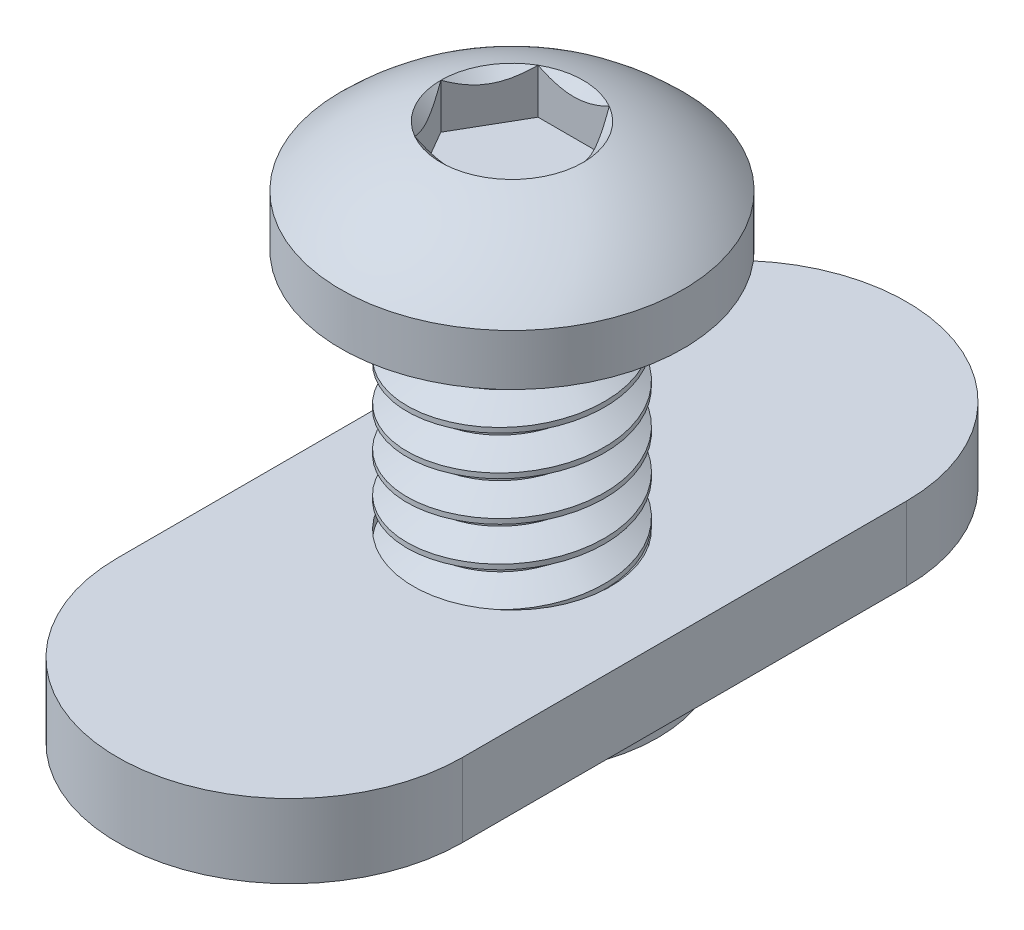
SolidWorks part; units mm, degrees
ref_plane "Front Plane" through (0, 0, 0) normal (0, 0, 1) x (1, 0, 0)
ref_plane "Top Plane" through (0, 0, 0) normal (0, 1, 0) x (1, 0, 0)
ref_plane "Right Plane" through (0, 0, 0) normal (1, 0, 0) x (0, 0, -1)
sketch "Sketch1" plane through (0, 0, 0) normal (0, 0, 1) x (1, 0, 0)
  line L0 (0, 0) -> (0, 53.1234) construction
  line L1 (0, 0) -> (-3.175, 0)
  line L2 (-3.175, 0) -> (-3.175, 12.7)
  line L3 (-3.175, 12.7) -> (-5.5118, 12.7)
  line L4 (-5.5118, 12.7) -> (-5.5118, 14.3459)
  line L5 (-5.5118, 14.3459) -> (-4.4094, 14.3459)
  line L6 (0, 0) -> (0, 16.8148)
  arc A0 (-4.4094, 14.3459) -> (0, 16.8148) centre (0, 11.6427) cw
  dimension "screw od" = 6.35
  dimension "head od" = 11.0236
  dimension "D3" = 8.8189
  dimension "D4" = 1.6459
  dimension "head height" = 4.1148
  dimension "screw length" = 12.7
sketch "Sketch2" plane through (0, 0, 0) normal (0, 0, 1) x (1, 0, 0)
  line L0 (0, 0) -> (0, 16.8148) construction
  line L1 (-3.175, 12.7) -> (-5.5118, 12.7) construction
  line L2 (0, 0) -> (-3.175, 0) construction
  line L3 (-3.175, 0) -> (-3.175, 12.7) construction
  line L4 (0, 0) -> (0, 12.7)
  line L5 (0, 12.7) -> (-3.175, 12.7)
  line L6 (0, 0) -> (-3.175, 0)
  line L7 (-3.175, 0) -> (-3.175, 12.7)
revolve "Revolve2" add sketch "Sketch2" angle 360 about L0
sketch "Sketch3" plane through (0, 12.7, 0) normal (0, 1, 0) x (1, 0, 0)
  circle A1 centre (0, 0) radius 3.175
  circle A2 centre (0, 0) radius 3.175
  dimension "D1" = 0
curve "Helix/Spiral1" pitch 1.27 height 17.4625 turns 13.75 parameters "pitch"=1.27
chamfer "Chamfer1" distance 1.27 angle 45 1 edges at (0, 0, -3.175)
sketch "Sketch4" plane through (0, 0, 0) normal (0, 0, 1) x (1, 0, 0)
  line L0 (3.175, 13.8112) -> (3.175, 12.7)
  line L1 (3.175, 12.7) -> (2.3501, 13.1762)
  line L2 (2.3501, 13.1762) -> (2.3501, 13.335)
  line L3 (2.3501, 13.335) -> (3.175, 13.8112)
  line L4 (2.3501, 13.2556) -> (3.175, 13.2556) construction
  line L5 (2.7626, 12.9381) -> (2.7626, 13.5731) construction
  line L7 (3.175, 12.7) -> (-3.175, 12.7) construction
  dimension "D1" = 60
  dimension "D2" = 0.1588
  dimension "D3" = 0.635
sweep "Cut-Sweep1" cut profiles "Sketch4" path "Helix/Spiral1"
sketch "Sketch5" plane through (0, 0, 0) normal (0, 0, 1) x (1, 0, 0)
  line L0 (0, 0) -> (0, 16.8148) construction
  line L1 (-3.175, 12.7) -> (-5.5118, 12.7) construction
  line L2 (-5.5118, 14.3459) -> (-4.4094, 14.3459) construction
  line L3 (-5.5118, 12.7) -> (-5.5118, 14.3459) construction
  line L4 (0, 12.7) -> (0, 16.8148)
  line L5 (0, 12.7) -> (-5.5118, 12.7)
  line L6 (-5.5118, 14.3459) -> (-4.4094, 14.3459)
  line L7 (-5.5118, 12.7) -> (-5.5118, 14.3459)
  arc A0 (0, 16.8148) -> (-4.4094, 14.3459) centre (0, 11.6427) ccw construction
  arc A1 (0, 16.8148) -> (-4.4094, 14.3459) centre (0, 11.6427) ccw
revolve "Revolve3" add sketch "Sketch5" angle 360 about L0
ref_plane "Plane1" through (0, 16.8148, 0) normal (0, 1, 0) x (-1, 0, 0)
sketch "Sketch6" plane through (0, 16.8148, 0) normal (0, 1, 0) x (-1, 0, 0)
  line L1 (1.1457, 1.9844) -> (-1.1457, 1.9844)
  line L2 (-1.1457, 1.9844) -> (-2.2914, 0)
  line L3 (-2.2914, 0) -> (-1.1457, -1.9844)
  line L4 (-1.1457, -1.9844) -> (1.1457, -1.9844)
  line L5 (1.1457, -1.9844) -> (2.2914, 0)
  line L6 (2.2914, 0) -> (1.1457, 1.9844)
  circle A0 centre (0, 0) radius 1.9844 construction
  dimension "hex" = 3.9688
extrude "Cut-Extrude1" cut sketch "Sketch6" against normal blind 1.9844
ref_plane "Plane2" through (0, 16.2795, 0) normal (0, 1, 0) x (-1, 0, 0)
sketch "Sketch7" plane through (0, 16.2795, 0) normal (0, 1, 0) x (-1, 0, 0)
  circle A0 centre (0, 0) radius 2.2914
extrude "Cut-Extrude2" cut sketch "Sketch7" against normal up to surface (1.4491 mm away) draft 45 and the other way through all
ref_plane "Plane3" through (0, 3.175, 0) normal (0, -1, 0) x (1, 0, 0)
sketch "Sketch8" plane through (0, 3.175, 0) normal (0, -1, 0) x (1, 0, 0)
  line L0 (0, -7.1437) -> (0, 7.1437) construction
  line L2 (-5.5563, 7.1437) -> (-5.5563, -7.1437)
  line L4 (5.5563, 7.1437) -> (5.5563, -7.1437)
  circle A0 centre (0, 0) radius 3.175
  arc A1 (-5.5563, 7.1437) -> (5.5563, 7.1437) centre (0, 7.1437) cw
  arc A2 (-5.5563, -7.1437) -> (5.5563, -7.1437) centre (0, -7.1437) ccw
  dimension "D1" = 6.35
  dimension "D3" = 25.4
  dimension "D2" = 11.1125
extrude "Extrude1" add sketch "Sketch8" along normal mid plane 3.4544 separate body
sketch "Sketch9" plane through (0, 1.4478, 0) normal (0, -1, 0) x (1, 0, 0)
  line L2 (5.5563, -7.1437) -> (5.5563, 7.1437)
  line L3 (-5.5563, 7.1437) -> (-5.5563, -7.1437)
  line L4 (5.5563, -7.1437) -> (5.5563, 7.1437)
  line L5 (-5.5563, 7.1437) -> (-5.5563, -7.1437)
  arc A2 (-5.5563, -7.1437) -> (5.5563, -7.1437) centre (0, -7.1437) ccw
  arc A3 (5.5563, 7.1437) -> (-5.5563, 7.1437) centre (0, 7.1437) ccw
  arc A4 (-5.5563, -7.1437) -> (5.5563, -7.1437) centre (0, -7.1437) ccw
  arc A5 (5.5563, 7.1437) -> (-5.5563, 7.1437) centre (0, 7.1437) ccw
  circle A6 centre (0, 0) radius 4.699
  circle A7 centre (0, 0) radius 4.699
  dimension "D1" = 0
  dimension "D2" = 1.524
extrude "Cut-Extrude3" cut sketch "Sketch9" against normal offset from surface (1.0795 mm away) 2.3749 up to face at (0, 4.9022, 0)
sketch "Sketch10" [suppressed] plane through (0, 7.9375, 0) normal (0, -1, 0) x (1, 0, 0)
  line L0 (-8.255, -12.3888) -> (-8.255, 2.8511)
  line L1 (8.255, 2.8511) -> (8.255, -12.3888)
  line L2 (-14.9844, 7.9311) -> (0, 7.9311) construction
  circle A0 centre (0, 0) radius 3.9688
  arc A1 (8.255, 2.8511) -> (-8.255, 2.8511) centre (0, -1.316) ccw
  arc A2 (-8.255, -12.3888) -> (8.255, -12.3888) centre (0, -8.2217) ccw
  dimension "D2" = 3.9624
  dimension "D3" = 16.51
  dimension "D4" = 5.08
  dimension "D5" = 6.35
  dimension "D1" = 25.4
extrude "Extrude2" [suppressed] add sketch "Sketch10" along normal mid plane 5.3594 separate body
sketch "Sketch11" [suppressed] plane through (0, 5.2578, 0) normal (0, -1, 0) x (1, 0, 0)
  line L2 (8.255, -12.3888) -> (8.255, 2.8511)
  line L3 (-8.255, 2.8512) -> (-8.255, -12.3888)
  line L4 (8.255, -12.3888) -> (8.255, 2.8511)
  line L5 (-8.255, 2.8512) -> (-8.255, -12.3888)
  circle A2 centre (0, 0) radius 5.4927
  circle A3 centre (0, 0) radius 5.4927
  arc A5 (-8.255, -12.3888) -> (8.255, -12.3888) centre (0, -8.2217) ccw
  arc A6 (8.255, 2.8511) -> (-8.255, 2.8512) centre (0, -1.316) ccw
  arc A7 (-8.255, -12.3888) -> (8.255, -12.3888) centre (0, -8.2217) ccw
  arc A8 (8.255, 2.8511) -> (-8.255, 2.8512) centre (0, -1.316) ccw
  dimension "D1" = 1.524
  dimension "D2" = 0
extrude "Cut-Extrude4" [suppressed] cut sketch "Sketch11" against normal offset from surface (1.651 mm away) 3.7084
sketch "Sketch12" [suppressed] plane through (0, 0, 0) normal (0, 0, 1) x (1, 0, 0)
  line L0 (-6.8072, 17.78) -> (-5.4458, 17.78) construction
  line L1 (-6.8072, 17.78) -> (-5.4458, 17.78)
  line L2 (9.2481, 20.0393) -> (-9.2481, 20.0393) construction
  line L3 (0, 0) -> (0, 53.1234) construction
  line L4 (-3.9688, 15.875) -> (-6.8072, 15.875) construction
  line L5 (-9.398, 15.875) -> (-3.9688, 15.875)
  line L6 (-9.398, 15.875) -> (-9.398, 14.605)
  line L7 (-9.398, 14.605) -> (-3.9688, 14.605)
  line L8 (-3.9688, 15.875) -> (-3.9688, 14.605)
  arc A0 (0, 20.6375) -> (-5.4458, 17.78) centre (0, 14.0195) ccw construction
  arc A1 (-2.7496, 20.0393) -> (-5.4458, 17.78) centre (0, 14.0195) ccw
  arc A2 (-6.8072, 17.78) -> (-2.7496, 20.0393) centre (0, 10.3277) cw
  dimension "D1" = 9.398
  dimension "D2" = 1.27
revolve "Revolve4" [suppressed] add sketch "Sketch12" angle 360 about L0
sketch "Sketch13" [suppressed] plane through (0, 6.35, 0) normal (0, -1, 0) x (1, 0, 0)
  line L0 (-7.9375, 4.7562) -> (-7.9375, -17.4688)
  line L1 (7.9375, 4.7562) -> (7.9375, -17.4688)
  circle A0 centre (0, 0) radius 3.9688
  arc A1 (-7.9375, 4.7562) -> (7.9375, 4.7562) centre (0, -3.5782) cw
  arc A2 (-7.9375, -17.4688) -> (7.9375, -17.4688) centre (0, -9.1345) ccw
  dimension "D2" = 28.575
  dimension "D3" = 3.9624
  dimension "D4" = 7.9375
  dimension "D1" = 15.875
  dimension "D5" = 3.175
extrude "Extrude4" [suppressed] add sketch "Sketch13" along normal mid plane 5.8928 separate body
sketch "Sketch14" [suppressed] plane through (0, 3.4036, 0) normal (0, -1, 0) x (1, 0, 0)
  line L2 (-7.9375, 4.7561) -> (-7.9375, -17.4688)
  line L3 (7.9375, -17.4688) -> (7.9375, 4.7562)
  line L4 (-7.9375, 4.7561) -> (-7.9375, -17.4688)
  line L5 (7.9375, -17.4688) -> (7.9375, 4.7562)
  arc A2 (7.9375, 4.7562) -> (-7.9375, 4.7561) centre (0, -3.5782) ccw
  arc A3 (-7.9375, -17.4688) -> (7.9375, -17.4688) centre (0, -9.1345) ccw
  arc A4 (7.9375, 4.7562) -> (-7.9375, 4.7561) centre (0, -3.5782) ccw
  arc A5 (-7.9375, -17.4688) -> (7.9375, -17.4688) centre (0, -9.1345) ccw
  circle A6 centre (0, 0) radius 5.4927
  circle A7 centre (0, 0) radius 5.4927
  dimension "D1" = 0
  dimension "D2" = 1.524
extrude "Cut-Extrude7" [suppressed] cut sketch "Sketch14" against normal offset from surface (1.8034 mm away) 4.0894
sketch "Sketch15" plane through (0, 0, 0) normal (0, 0, 1) x (1, 0, 0)
  line L0 (-5.5118, 14.3459) -> (-4.4094, 14.3459) construction
  line L1 (-5.5118, 14.3459) -> (-4.4094, 14.3459)
  line L2 (10.3378, 16.2795) -> (-10.3378, 16.2795) construction
  line L3 (0, 0) -> (0, 53.1234) construction
  arc A0 (0, 16.8148) -> (-4.4094, 14.3459) centre (0, 11.6427) ccw construction
  arc A1 (-2.2914, 16.2795) -> (-4.4094, 14.3459) centre (0, 11.6427) ccw
  arc A2 (-2.2914, 16.2795) -> (-5.5118, 14.3459) centre (0, 8.8147) ccw
revolve "Revolve5" add sketch "Sketch15" angle 360 about L0
sketch "Sketch16" [suppressed] plane through (0, 3.175, 0) normal (0, -1, 0) x (1, 0, 0)
  line L0 (-6.3881, 8.443) -> (-6.3881, -33.843)
  line L1 (6.3881, 8.443) -> (6.3881, -33.843)
  line L2 (0, -25.4) -> (0, 0) construction
  line L3 (0, -12.7) -> (-6.3881, -12.7) construction
  line L4 (-6.3881, -27.1355) -> (-6.3881, 1.7355) construction
  circle A0 centre (0, 0) radius 3.175
  circle A1 centre (0, -25.4) radius 3.175
  arc A2 (-6.3881, 8.443) -> (6.3881, 8.443) centre (0, 1.7355) cw
  arc A3 (-6.3881, -33.843) -> (6.3881, -33.843) centre (0, -27.1355) ccw
  dimension "D1" = 25.4
  dimension "D2" = 6.35
  dimension "D4" = 47.3964
  dimension "D3" = 12.7762
  dimension "D5" = 2.5552
extrude "Extrude5" [suppressed] add sketch "Sketch16" along normal mid plane 4.0894 separate body
sketch "Sketch17" [suppressed] plane through (0, 1.1303, 0) normal (0, -1, 0) x (1, 0, 0)
  line L2 (-6.3881, 8.443) -> (-6.3881, -33.843)
  line L3 (6.3881, -33.843) -> (6.3881, 8.443)
  line L4 (-6.3881, 8.443) -> (-6.3881, -33.843)
  line L5 (6.3881, -33.843) -> (6.3881, 8.443)
  arc A2 (6.3881, 8.443) -> (-6.3881, 8.443) centre (0, 1.7355) ccw
  arc A3 (-6.3881, -33.843) -> (6.3881, -33.843) centre (0, -27.1355) ccw
  arc A4 (6.3881, 8.443) -> (-6.3881, 8.443) centre (0, 1.7355) ccw
  arc A5 (-6.3881, -33.843) -> (6.3881, -33.843) centre (0, -27.1355) ccw
  circle A6 centre (0, -25.4) radius 4.699
  circle A7 centre (0, -25.4) radius 4.699
  circle A10 centre (0, 0) radius 4.699
  circle A11 centre (0, 0) radius 4.699
  dimension "D1" = 0
  dimension "D2" = 1.524
  dimension "D3" = 1.524
pattern_linear "LPattern1" [suppressed] count 2 spacing 25.4
extrude "Cut-Extrude9" [suppressed] cut sketch "Sketch17" against normal offset from surface (1.4224 mm away) 2.667
sketch "Sketch18" [suppressed] plane through (0, 7.9375, 0) normal (0, -1, 0) x (1, 0, 0)
  line L0 (-7.9375, 13.462) -> (-7.9375, -51.562)
  line L1 (7.9375, 13.462) -> (7.9375, -51.562)
  line L2 (0, 0) -> (0, -38.1) construction
  line L3 (0, -19.05) -> (-7.9375, -19.05) construction
  line L4 (0, -19.05) -> (7.9375, -19.05) construction
  circle A0 centre (0, 0) radius 3.9688
  circle A1 centre (0, -38.1) radius 3.9688
  arc A2 (-7.9375, 13.462) -> (7.9375, 13.462) centre (0, 5.1276) cw
  arc A3 (-7.9375, -51.562) -> (7.9375, -51.562) centre (0, -43.2276) ccw
  dimension "D1" = 38.1
  dimension "D2" = 7.9375
  dimension "D4" = 3.175
  dimension "D5" = 71.374
  dimension "D3" = 15.875
extrude "Extrude6" [suppressed] add sketch "Sketch18" along normal mid plane 5.9944 separate body
sketch "Sketch19" [suppressed] plane through (0, 4.9403, 0) normal (0, -1, 0) x (1, 0, 0)
  line L2 (-7.9375, 13.462) -> (-7.9375, -51.562)
  line L3 (7.9375, -51.562) -> (7.9375, 13.462)
  line L4 (-7.9375, 13.462) -> (-7.9375, -51.562)
  line L5 (7.9375, -51.562) -> (7.9375, 13.462)
  arc A2 (7.9375, 13.462) -> (-7.9375, 13.462) centre (0, 5.1276) ccw
  arc A3 (-7.9375, -51.562) -> (7.9375, -51.562) centre (0, -43.2276) ccw
  arc A4 (7.9375, 13.462) -> (-7.9375, 13.462) centre (0, 5.1276) ccw
  arc A5 (-7.9375, -51.562) -> (7.9375, -51.562) centre (0, -43.2276) ccw
  circle A6 centre (0, 0) radius 5.4927
  circle A7 centre (0, 0) radius 5.4927
  circle A9 centre (0, -38.1) radius 5.4928
  circle A10 centre (0, -38.1) radius 5.4928
  dimension "D1" = 0
  dimension "D2" = 1.524
  dimension "D3" = 1.524
extrude "Cut-Extrude10" [suppressed] cut sketch "Sketch19" against normal offset from surface (2.1844 mm away) 3.81
pattern_linear "LPattern2" [suppressed] count 2 spacing 38.1
equation "\"D2@Sketch4\" = \"pitch@Helix/Spiral1\"*.125"
equation "\"D3@Sketch4\" = \"pitch@Helix/Spiral1\"*.5"
equation "\"D3@Helix/Spiral1\" = \"screw length@Sketch1\"+.18750"
equation "\"D1@Chamfer1\" = \"pitch@Helix/Spiral1\""
equation "\"D1@Cut-Extrude1\" = \"hex@Sketch6\"/2"
equation "\"D1@Sketch8\" = \"screw od@Sketch1\""
equation "\"D4@Sketch1\" = \"head height@Sketch1\"/2.5"
equation "\"D3@Sketch1\" = \"head od@Sketch1\"*.8"
equation "\"D5@Sketch10\" = \"screw od@Sketch1\""
equation "\"D4@Sketch10\" = \"D1@Sketch10\"*.2"
equation "\"D5@Sketch13\" = \"D1@Sketch13\"*.2"
equation "\"D5@Sketch16\" = \"D3@Sketch16\"*.2"
equation "\"D4@Sketch18\" = \"D3@Sketch18\"*.2"
